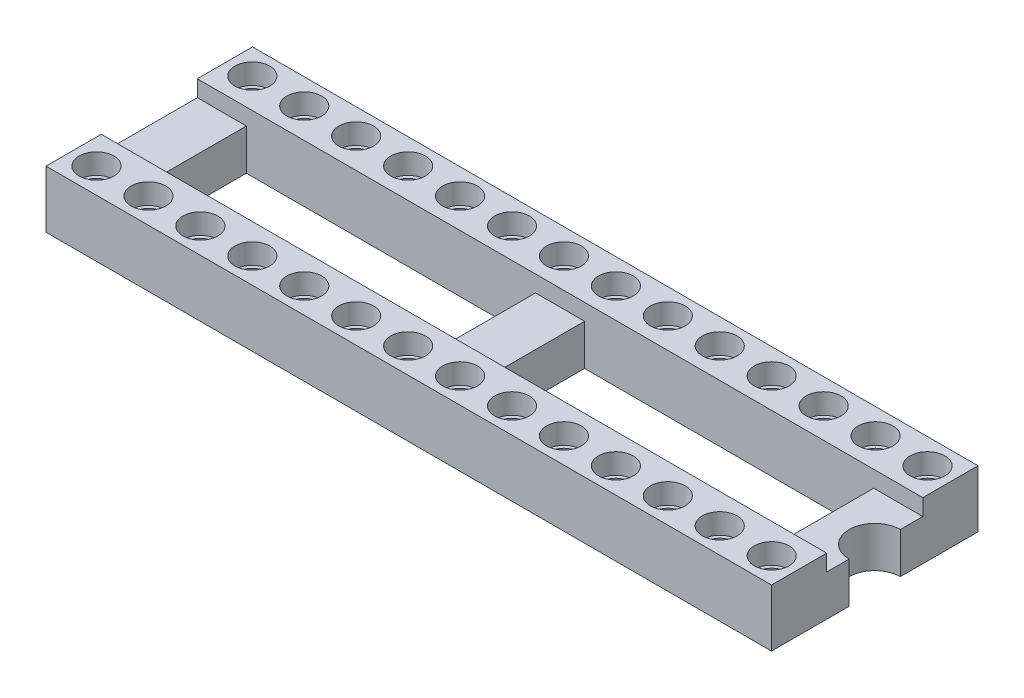
SolidWorks part; units mm, degrees
ref_plane "Front Plane" through (0, 0, 0) normal (0, 0, 1) x (1, 0, 0)
ref_plane "Top Plane" through (0, 0, 0) normal (0, 1, 0) x (1, 0, 0)
ref_plane "Right Plane" through (0, 0, 0) normal (1, 0, 0) x (0, 0, -1)
sketch "Sketch1" plane through (0, 0, 0) normal (1, 0, 0) x (0, 0, -1)
  line L0 (-5.05, 0) -> (5.05, 0)
  line L1 (55, 0) -> (-55, 0) construction
  line L2 (-5.05, 0) -> (-5.05, 2.8)
  line L3 (-5.05, 2.8) -> (-2.35, 2.8)
  line L4 (-2.35, 2.8) -> (-2.35, 2)
  line L5 (-2.35, 2) -> (2.35, 2)
  line L6 (2.35, 2) -> (2.35, 2.8)
  line L7 (2.35, 2.8) -> (5.05, 2.8)
  line L8 (5.05, 2.8) -> (5.05, 0)
  dimension "D1" = 10.1
  dimension "D2" = 4.7
  dimension "D3" = 2
  dimension "D4" = 2.8
extrude "Boss-Extrude1" add sketch "Sketch1" along normal mid plane 35.48
sketch "Sketch2" plane through (0, 2, 0) normal (0, 1, 0) x (1, 0, 0)
  line L0 (17.74, 2.35) -> (-17.74, 2.35) construction
  line L1 (-15.34, 2.35) -> (-1.2, 2.35)
  line L2 (-15.34, 2.35) -> (-15.34, -2.35)
  line L3 (-15.34, -2.35) -> (-1.2, -2.35)
  line L4 (15.34, 2.35) -> (15.34, -2.35)
  line L5 (17.74, -2.35) -> (-17.74, -2.35) construction
  line L6 (17.74, 2.35) -> (17.74, -2.35) construction
  line L7 (-17.74, 2.35) -> (-17.74, -2.35) construction
  line L8 (-1.2, 2.35) -> (-1.2, -2.35)
  line L9 (1.2, 2.35) -> (1.2, -2.35)
  line L10 (0, -1.54) -> (0, 1.54) construction
  line L11 (1.2, 2.35) -> (15.34, 2.35)
  line L12 (1.2, -2.35) -> (15.34, -2.35)
  dimension "D1" = 2.4
  dimension "D2" = 30.68
  dimension "D3" = 2.4
  dimension "D4" = 2.4
  dimension "D5" = 1.2
extrude "Cut-Extrude1" cut sketch "Sketch2" against normal blind 35.5
sketch "Sketch3" plane through (0, 2, 0) normal (0, 1, 0) x (1, 0, 0)
  line L0 (-1.54, 0) -> (1.54, 0) construction
  line L1 (17.74, 2.35) -> (17.74, -2.35) construction
  circle A0 centre (17.74, 0) radius 1.25
  dimension "D1" = 2.5
extrude "Cut-Extrude2" cut sketch "Sketch3" against normal blind 35.5
hole_wizard "hole" positions "Sketch5" profile "Sketch4" counterbore size "M5" standard "ISO" end condition through all
sketch "Sketch5" plane through (0, 2.8, 0) normal (0, 1, 0) x (1, 0, 0)
  line L0 (0, -1.54) -> (0, 1.54) construction
  line L1 (-1.54, 0) -> (1.54, 0) construction
  point P0 (16.51, 3.81)
  dimension "D1" = 16.51
  dimension "D2" = 3.81
sketch "Sketch4" plane through (16.51, 2.8, -3.81) normal (1, 0, 0) x (0, 0, 1)
  line L0 (0, 0) -> (0, 2.8)
  line L1 (0, 2.8) -> (0.675, 2.8)
  line L3 (0.675, 2.8) -> (0.675, 1)
  line L4 (0.675, 1) -> (0.85, 1)
  line L5 (0.85, 1) -> (0.85, 0)
  line L7 (0.85, 0) -> (0, 0)
  line L11 (0, -6.35) -> (0, 107.95) construction
  dimension "Thru Hole Dia." = 1.35
  dimension "Thru Hole Depth" = 2.8
  dimension "C'Bore Dia." = 1.7
  dimension "C'Bore Depth" = 1
pattern_linear "LPattern1" count 14 spacing 2.54 along (-1, 0, 0) count 2 spacing 7.62 along (0, 0, 1) of "hole"
